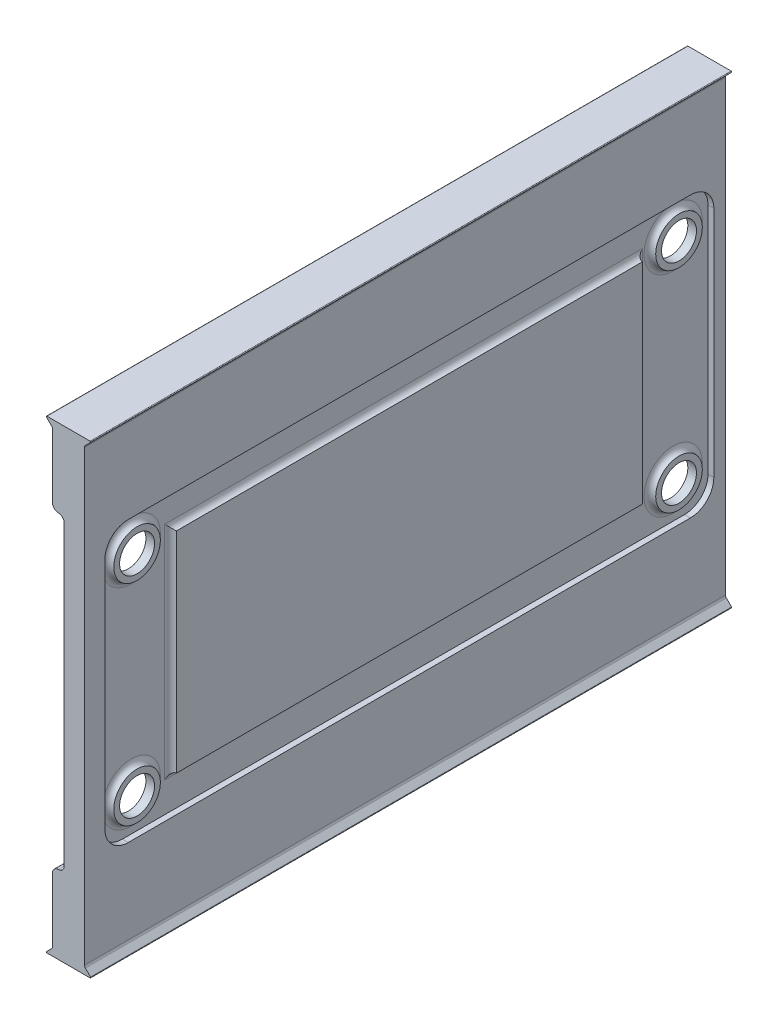
SolidWorks part; units mm, degrees
ref_plane "Front Plane" through (0, 0, 0) normal (0, 0, 1) x (1, 0, 0)
ref_plane "Top Plane" through (0, 0, 0) normal (0, 1, 0) x (1, 0, 0)
ref_plane "Right Plane" through (0, 0, 0) normal (1, 0, 0) x (0, 0, -1)
sketch "Sketch1" plane through (0, 0, 0) normal (0, 0, 1) x (1, 0, 0)
  line L0 (-1.8543, 19.9437) -> (1.8543, 19.9437)
  line L1 (0, 22.5) -> (0, -22.5) construction
  line L2 (-1.8896, 19.8583) -> (-1.4447, 19.4133)
  line L7 (1.8896, 19.8583) -> (1.4447, 19.4133)
  line L8 (-20, 0) -> (20, 0) construction
  line L11 (-1.8896, -19.8583) -> (-1.4447, -19.4133)
  line L12 (-1.8543, -19.9437) -> (1.8543, -19.9437)
  line L13 (1.8896, -19.8583) -> (1.4447, -19.4133)
  line L16 (-1.3714, 19.2366) -> (-1.3714, -19.2366)
  line L17 (1.3714, 19.2366) -> (1.3714, -19.2366)
  arc A3 (-1.4447, 19.4133) -> (-1.3714, 19.2366) centre (-1.6214, 19.2366) cw
  arc A7 (1.4447, 19.4133) -> (1.3714, 19.2366) centre (1.6214, 19.2366) ccw
  arc A8 (1.8543, 19.9437) -> (1.8896, 19.8583) centre (1.8543, 19.8937) cw
  arc A9 (-1.8543, 19.9437) -> (-1.8896, 19.8583) centre (-1.8543, 19.8937) ccw
  arc A12 (-1.4447, -19.4133) -> (-1.3714, -19.2366) centre (-1.6214, -19.2366) ccw
  arc A13 (-1.8543, -19.9437) -> (-1.8896, -19.8583) centre (-1.8543, -19.8937) cw
  arc A14 (1.8543, -19.9437) -> (1.8896, -19.8583) centre (1.8543, -19.8937) ccw
  arc A15 (1.4447, -19.4133) -> (1.3714, -19.2366) centre (1.6214, -19.2366) cw
  point P0 (1.3714, 0)
  point P1 (0, 0)
  point P8 (0, 19.9437)
  point P30 (1.975, 19.9437)
  point P33 (-1.975, 19.9437)
  dimension "D1" = 39.8873
  dimension "D2" = 2.7429
  dimension "D7" = 0.7071
  dimension "D8" = 0.25
  dimension "D9" = 0.05
  dimension "D3" = 3.95
  dimension "D4" = 45
extrude "Boss-Extrude1" add sketch "Sketch1" along normal blind 55
sketch "Sketch2" plane through (1.3714, 0, 0) normal (1, 0, 0) x (0, 0, -1)
  line L0 (-71.3614, -146.3971) -> (297.3053, -146.3971) construction
  line L5 (-50.4885, 9.0879) -> (-50.4885, -8.9121) construction
  line L6 (-51.25, 12) -> (-3, 12)
  line L7 (-53.25, 10) -> (-53.25, -10)
  line L8 (-51.25, -12) -> (-3, -12)
  line L9 (-1, 10) -> (-1, -10)
  line L10 (-50.4885, 9.0879) -> (-3.9885, 9.0879) construction
  line L11 (-55, -19.2366) -> (-55, 19.2366) construction
  line L13 (-3.9885, 9.0879) -> (-3.9885, -8.9121) construction
  line L14 (-27.125, 9.0879) -> (-27.125, -8.9121) construction
  line L15 (-47.125, 9.0879) -> (-7.125, 9.0879)
  line L16 (-47.125, 9.0879) -> (-47.125, -8.9121)
  line L17 (-47.125, -8.9121) -> (-7.125, -8.9121)
  line L18 (-7.125, 9.0879) -> (-7.125, -8.9121)
  line L19 (-53.25, 0) -> (-31.25, 0) construction
  arc A0 (-53.25, 10) -> (-51.25, 12) centre (-51.25, 10) cw
  arc A1 (-3, 12) -> (-1, 10) centre (-3, 10) cw
  arc A2 (-1, -10) -> (-3, -12) centre (-3, -10) cw
  circle A3 centre (-50.4885, 9.0879) radius 2
  circle A4 centre (-50.4885, -8.9121) radius 2
  circle A5 centre (-3.9885, -8.9121) radius 2
  circle A6 centre (-3.9885, 9.0879) radius 2
  arc A7 (-51.25, -12) -> (-53.25, -10) centre (-51.25, -10) cw
  point P12 (-1, -12)
  point P23 (-55, 0)
  point P31 (-27.125, 12)
  point P34 (-53.25, -12)
  dimension "D1" = 24
  dimension "D3" = 2
  dimension "D10" = 4
  dimension "D11" = 4
  dimension "D12" = 4
  dimension "D13" = 4
  dimension "D18" = 2
  dimension "D2" = 52.25
  dimension "D4" = 18
  dimension "D5" = 46.5
  dimension "D6" = 2.9121
  dimension "D7" = 2.7615
  dimension "D8" = 1.75
  dimension "D14" = 18
  dimension "D15" = 46.5
  dimension "D16" = 40
  dimension "D17" = 18
sketch "Sketch4" plane through (-1.3714, 0, 0) normal (-1, 0, 0) x (0, 0, 1)
  line L0 (116.9009, 229.5811) -> (508.9009, 229.5811) construction
  line L5 (-215.0482, -19.301) -> (-235.2775, 269.9925) construction
extrude "Cut-Extrude4" cut sketch "Sketch2" against normal blind 0.5
sketch "Sketch7" plane through (1.3714, 0, 0) normal (1, 0, 0) x (0, 0, -1)
  circle A0 centre (-50.4885, 9.0879) radius 1.5
  circle A1 centre (-3.9885, 9.0879) radius 1.5
  circle A2 centre (-3.9885, -8.9121) radius 1.5
  circle A3 centre (-50.4885, -8.9121) radius 1.5
  dimension "D1" = 3
  dimension "D2" = 3
  dimension "D3" = 3
  dimension "D4" = 3
extrude "Cut-Extrude7" cut sketch "Sketch7" against normal through all
sketch "Sketch8" plane through (-1.3714, 0, 0) normal (-1, 0, 0) x (0, 0, 1)
  circle A0 centre (3.9885, 9.0879) radius 3.75
  circle A1 centre (3.9885, -8.9121) radius 3.75
  circle A2 centre (50.4885, 9.0879) radius 3.75
  circle A3 centre (50.4885, -8.9121) radius 3.75
  dimension "D1" = 7.5
  dimension "D2" = 7.5
  dimension "D3" = 7.5
  dimension "D4" = 7.5
extrude "Cut-Extrude8" cut sketch "Sketch8" against normal blind 2
sketch "Sketch9" plane through (-1.3714, 0, 0) normal (-1, 0, 0) x (0, 0, 1)
  line L0 (0, 0) -> (55, 0) construction
  line L1 (55, 19.2366) -> (55, -19.2366) construction
  line L2 (0, 19.2366) -> (0, -19.2366) construction
  line L3 (55, 13.25) -> (0, 13.25)
  line L4 (55, 13.25) -> (55, -13.25)
  line L5 (55, -13.25) -> (0, -13.25)
  line L6 (0, 13.25) -> (0, -13.25)
  line L7 (55, 13.25) -> (0, -13.25) construction
  line L8 (55, -13.25) -> (0, 13.25) construction
  point P5 (27.5, 0)
  dimension "D1" = 26.5
extrude "Cut-Extrude9" cut sketch "Sketch9" against normal blind 1
fillet "Fillet1" radius 0.5 2 edges at (-0.3714, -13.25, 27.5) (-0.3714, 13.25, 27.5)
fillet "Fillet2" radius 0.5 2 edges at (-1.3714, -13.25, 27.5) (-1.3714, 13.25, 27.5)
fillet "Fillet3" radius 0.5 4 edges at (0.8714, -6.9121, 50.4885) (0.8714, 11.0879, 50.4885) (0.8714, 11.0879, 3.9885) (0.8714, -6.9121, 3.9885)
fillet "Fillet4" radius 0.5 4 edges at (0.8714, 0.0879, 7.125) (0.8714, -8.9121, 27.125) (0.8714, 9.0879, 27.125) (0.8714, 0.0879, 47.125)
fillet "Fillet5" radius 0.5 4 edges at (0.6286, 5.3379, 3.9885) (0.6286, -12.6621, 3.9885) (0.6286, -12.6621, 50.4885) (0.6286, 5.3379, 50.4885)
